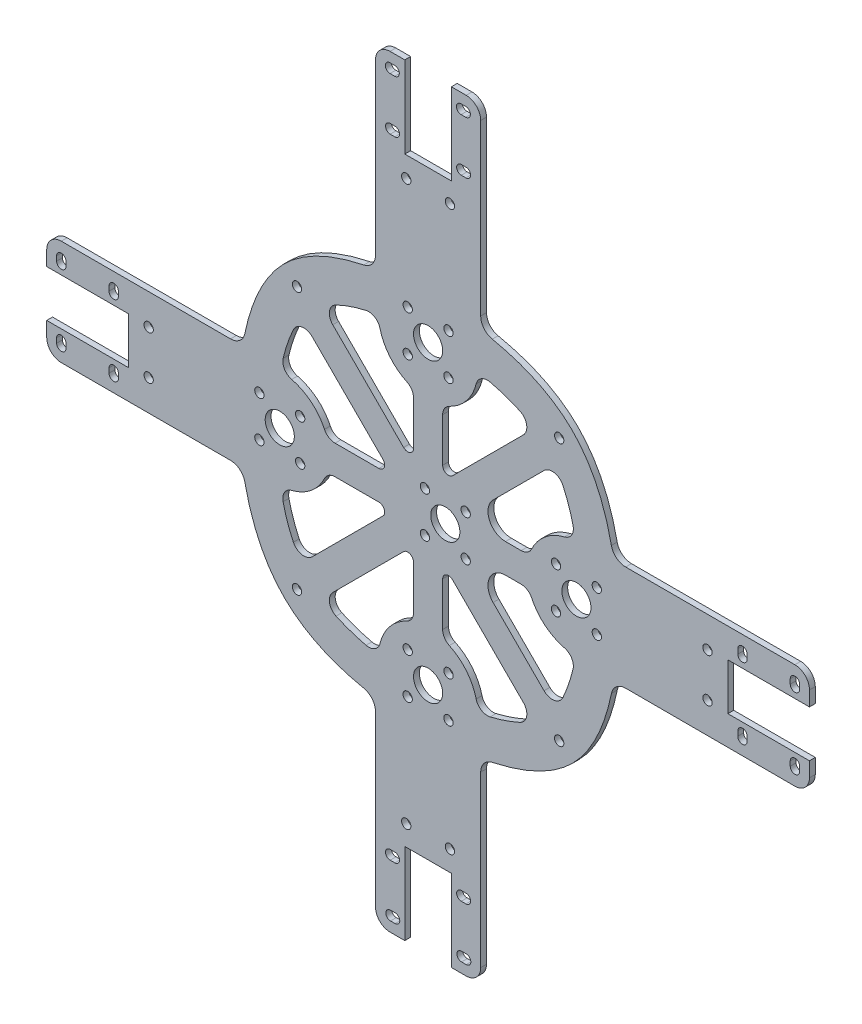
SolidWorks part; units mm, degrees
ref_plane "Front Plane" through (0, 0, 0) normal (0, 0, 1) x (1, 0, 0)
ref_plane "Top Plane" through (0, 0, 0) normal (0, 1, 0) x (1, 0, 0)
ref_plane "Right Plane" through (0, 0, 0) normal (1, 0, 0) x (0, 0, -1)
sketch "Sketch1" plane through (0, 0, 157.1733) normal (0, 0, 1) x (1, 0, 0)
  line L0 (24.8571, 138.0093) -> (24.8571, 36.186) construction
  line L1 (75.7688, 87.0977) -> (-26.0546, 87.0977) construction
  line L2 (24.8571, 87.0977) -> (74.3546, 136.5951) construction
  line L3 (24.8571, 87.0977) -> (-24.6404, 136.5951) construction
  line L4 (24.8571, 87.0977) -> (74.3546, 37.6002) construction
  line L5 (24.8571, 87.0977) -> (-24.6404, 37.6002) construction
  line L6 (24.8571, 36.186) -> (24.8571, -73.1097) construction
  line L7 (-4.7101, -8.814) -> (52.2591, -8.814) construction
  line L8 (6.7991, -38.814) -> (6.7991, 19.2863)
  line L9 (32.8571, -43.814) -> (37.9151, -43.814)
  line L10 (42.9151, -38.814) -> (42.9151, 19.2918)
  line L11 (11.7991, -43.814) -> (16.8571, -43.814)
  line L12 (16.8571, -43.814) -> (16.8571, -15.814)
  line L13 (16.8571, -15.814) -> (32.8571, -15.814)
  line L14 (32.8571, -15.814) -> (32.8571, -43.814)
  line L15 (11.8571, -19.214) -> (13.4571, -19.214)
  line L16 (13.4571, -22.414) -> (11.8571, -22.414)
  line L17 (37.8571, -19.214) -> (36.2571, -19.214)
  line L18 (37.8571, -22.414) -> (36.2571, -22.414)
  line L19 (37.9382, -40.414) -> (36.3382, -40.414)
  line L20 (13.5382, -40.414) -> (11.9382, -40.414)
  line L21 (-101.0546, 105.1556) -> (-42.9534, 105.1556)
  line L22 (11.9382, -37.214) -> (13.5382, -37.214)
  line L23 (37.9382, -37.214) -> (36.3382, -37.214)
  line L24 (-106.0546, 79.0977) -> (-106.0546, 74.0397)
  line L25 (-101.0546, 69.0397) -> (-42.9487, 69.0397)
  line L26 (-106.0546, 100.1556) -> (-106.0546, 95.0977)
  line L27 (-106.0546, 95.0977) -> (-78.0546, 95.0977)
  line L28 (-78.0546, 95.0977) -> (-78.0546, 79.0977)
  line L29 (-78.0546, 79.0977) -> (-106.0546, 79.0977)
  line L30 (-81.4546, 100.0977) -> (-81.4546, 98.4977)
  line L31 (-84.6546, 98.4977) -> (-84.6546, 100.0977)
  line L32 (-81.4546, 74.0977) -> (-81.4546, 75.6977)
  line L33 (-84.6546, 74.0977) -> (-84.6546, 75.6977)
  line L34 (-102.6546, 74.0165) -> (-102.6546, 75.6165)
  line L35 (-102.6546, 98.4165) -> (-102.6546, 100.0165)
  line L36 (-99.4546, 100.0165) -> (-99.4546, 98.4165)
  line L37 (-99.4546, 74.0165) -> (-99.4546, 75.6165)
  line L38 (-26.0546, 87.0977) -> (-135.3502, 87.0977) construction
  line L39 (-71.0546, 116.6649) -> (-71.0546, 59.6957) construction
  line L40 (42.9151, 213.0093) -> (42.9151, 154.909)
  line L41 (16.8571, 218.0093) -> (11.7991, 218.0093)
  line L42 (6.7991, 213.0093) -> (6.7991, 154.9075)
  line L43 (37.9151, 218.0093) -> (32.8571, 218.0093)
  line L44 (32.8571, 218.0093) -> (32.8571, 190.0093)
  line L45 (32.8571, 190.0093) -> (16.8571, 190.0093)
  line L46 (16.8571, 190.0093) -> (16.8571, 218.0093)
  line L47 (37.8571, 193.4093) -> (36.2571, 193.4093)
  line L48 (36.2571, 196.6093) -> (37.8571, 196.6093)
  line L49 (11.8571, 193.4093) -> (13.4571, 193.4093)
  line L50 (11.8571, 196.6093) -> (13.4571, 196.6093)
  line L51 (11.776, 214.6093) -> (13.376, 214.6093)
  line L52 (36.176, 214.6093) -> (37.776, 214.6093)
  line L53 (37.776, 211.4093) -> (36.176, 211.4093)
  line L54 (11.776, 211.4093) -> (13.376, 211.4093)
  line L55 (24.8571, 138.0093) -> (24.8571, 247.305) construction
  line L56 (54.4243, 183.0093) -> (-2.5449, 183.0093) construction
  line L57 (150.7688, 69.0397) -> (92.7039, 69.1257)
  line L58 (155.7688, 95.0977) -> (155.7688, 100.1556)
  line L59 (150.7688, 105.1556) -> (92.6636, 105.1556)
  line L60 (155.7688, 74.0397) -> (155.7688, 79.0977)
  line L61 (155.7688, 79.0977) -> (127.7688, 79.0977)
  line L62 (127.7688, 79.0977) -> (127.7688, 95.0977)
  line L63 (127.7688, 95.0977) -> (155.7688, 95.0977)
  line L64 (131.1688, 74.0977) -> (131.1688, 75.6977)
  line L65 (134.3688, 75.6977) -> (134.3688, 74.0977)
  line L66 (131.1688, 100.0977) -> (131.1688, 98.4977)
  line L67 (134.3688, 100.0977) -> (134.3688, 98.4977)
  line L68 (152.3688, 100.1788) -> (152.3688, 98.5788)
  line L69 (152.3688, 75.7788) -> (152.3688, 74.1788)
  line L70 (149.1688, 74.1788) -> (149.1688, 75.7788)
  line L71 (149.1688, 100.1788) -> (149.1688, 98.5788)
  line L72 (75.7688, 87.0977) -> (185.0644, 87.0977) construction
  line L73 (120.7688, 57.5304) -> (120.7688, 114.4996) construction
  line L76 (-42.9487, 69.0397) -> (-42.9427, 69.0397)
  line L81 (42.9151, 154.909) -> (42.9151, 154.9053)
  circle A0 centre (17.3571, -8.814) radius 1.6
  circle A1 centre (32.3571, -8.814) radius 1.6
  arc A2 (42.9151, 19.2918) -> (46.8658, 24.1805) centre (47.9151, 19.2918) cw
  arc A3 (6.7991, 19.2863) -> (2.7951, 24.1861) centre (1.7991, 19.2863) ccw
  arc A4 (42.9151, -38.814) -> (37.9151, -43.814) centre (37.9151, -38.814) cw
  arc A5 (6.7991, -38.814) -> (11.7991, -43.814) centre (11.7991, -38.814) ccw
  arc A6 (11.8571, -19.214) -> (11.8571, -22.414) centre (11.8571, -20.814) ccw
  arc A7 (11.9382, -37.214) -> (11.9382, -40.414) centre (11.9382, -38.814) ccw
  arc A8 (37.8571, -19.214) -> (37.8571, -22.414) centre (37.8571, -20.814) cw
  arc A9 (36.3382, -40.414) -> (36.3382, -37.214) centre (36.3382, -38.814) cw
  arc A10 (13.5382, -40.414) -> (13.5382, -37.214) centre (13.5382, -38.814) ccw
  arc A11 (13.4571, -22.414) -> (13.4571, -19.214) centre (13.4571, -20.814) ccw
  arc A12 (37.9382, -37.214) -> (37.9382, -40.414) centre (37.9382, -38.814) cw
  arc A13 (36.2571, -22.414) -> (36.2571, -19.214) centre (36.2571, -20.814) cw
  circle A14 centre (-71.0546, 94.5977) radius 1.6
  circle A15 centre (-71.0546, 79.5977) radius 1.6
  arc A16 (-38.0477, 65.0591) -> (-42.9427, 69.0397) centre (-42.9427, 64.0397) ccw
  arc A17 (46.8977, 150.0099) -> (42.9151, 154.9053) centre (47.9151, 154.9053) cw
  arc A18 (-101.0546, 69.0397) -> (-106.0546, 74.0397) centre (-101.0546, 74.0397) cw
  arc A19 (-101.0546, 105.1556) -> (-106.0546, 100.1556) centre (-101.0546, 100.1556) ccw
  arc A20 (-81.4546, 100.0977) -> (-84.6546, 100.0977) centre (-83.0546, 100.0977) ccw
  arc A21 (-99.4546, 100.0165) -> (-102.6546, 100.0165) centre (-101.0546, 100.0165) ccw
  arc A22 (-81.4546, 74.0977) -> (-84.6546, 74.0977) centre (-83.0546, 74.0977) cw
  arc A23 (-102.6546, 75.6165) -> (-99.4546, 75.6165) centre (-101.0546, 75.6165) cw
  arc A24 (-102.6546, 98.4165) -> (-99.4546, 98.4165) centre (-101.0546, 98.4165) ccw
  arc A25 (-84.6546, 98.4977) -> (-81.4546, 98.4977) centre (-83.0546, 98.4977) ccw
  arc A26 (-99.4546, 74.0165) -> (-102.6546, 74.0165) centre (-101.0546, 74.0165) cw
  arc A27 (-84.6546, 75.6977) -> (-81.4546, 75.6977) centre (-83.0546, 75.6977) cw
  circle A28 centre (32.3571, 183.0093) radius 1.6
  circle A29 centre (17.3571, 183.0093) radius 1.6
  arc A30 (87.7994, 65.1351) -> (92.7039, 69.1257) centre (92.6965, 64.1258) cw
  arc A31 (87.7682, 109.1387) -> (92.6636, 105.1556) centre (92.6636, 110.1556) ccw
  arc A32 (6.7991, 213.0093) -> (11.7991, 218.0093) centre (11.7991, 213.0093) cw
  arc A33 (42.9151, 213.0093) -> (37.9151, 218.0093) centre (37.9151, 213.0093) ccw
  arc A34 (37.8571, 193.4093) -> (37.8571, 196.6093) centre (37.8571, 195.0093) ccw
  arc A35 (37.776, 211.4093) -> (37.776, 214.6093) centre (37.776, 213.0093) ccw
  arc A36 (11.8571, 193.4093) -> (11.8571, 196.6093) centre (11.8571, 195.0093) cw
  arc A37 (13.376, 214.6093) -> (13.376, 211.4093) centre (13.376, 213.0093) cw
  arc A38 (36.176, 214.6093) -> (36.176, 211.4093) centre (36.176, 213.0093) ccw
  arc A39 (36.2571, 196.6093) -> (36.2571, 193.4093) centre (36.2571, 195.0093) ccw
  arc A40 (11.776, 211.4093) -> (11.776, 214.6093) centre (11.776, 213.0093) cw
  arc A41 (13.4571, 196.6093) -> (13.4571, 193.4093) centre (13.4571, 195.0093) cw
  circle A42 centre (120.7688, 79.5977) radius 1.6
  circle A43 centre (120.7688, 94.5977) radius 1.6
  arc A44 (2.8163, 150.012) -> (6.7991, 154.9075) centre (1.7991, 154.9075) ccw
  arc A45 (-38.058, 109.1381) -> (-42.9534, 105.1556) centre (-42.9534, 110.1556) cw
  arc A46 (150.7688, 105.1556) -> (155.7688, 100.1556) centre (150.7688, 100.1556) cw
  arc A47 (150.7688, 69.0397) -> (155.7688, 74.0397) centre (150.7688, 74.0397) ccw
  arc A48 (131.1688, 74.0977) -> (134.3688, 74.0977) centre (132.7688, 74.0977) ccw
  arc A49 (149.1688, 74.1788) -> (152.3688, 74.1788) centre (150.7688, 74.1788) ccw
  arc A50 (131.1688, 100.0977) -> (134.3688, 100.0977) centre (132.7688, 100.0977) cw
  arc A51 (152.3688, 98.5788) -> (149.1688, 98.5788) centre (150.7688, 98.5788) cw
  arc A52 (152.3688, 75.7788) -> (149.1688, 75.7788) centre (150.7688, 75.7788) ccw
  arc A53 (134.3688, 75.6977) -> (131.1688, 75.6977) centre (132.7688, 75.6977) ccw
  arc A54 (149.1688, 100.1788) -> (152.3688, 100.1788) centre (150.7688, 100.1788) cw
  arc A55 (134.3688, 98.4977) -> (131.1688, 98.4977) centre (132.7688, 98.4977) cw
  spline S0 degree 3 poles (46.8658, 24.1805) (57.6421, 26.4935) (77.1441, 34.8421) (85.5664, 54.301) (87.7994, 65.1351) knots 0.049347 0.049347 0.049347 0.049347 0.125 0.200866 0.200866 0.200866 0.200866
  spline S1 degree 3 poles (-38.0477, 65.0591) (-35.8019, 54.2758) (-27.373, 34.8677) (-8.0057, 26.3816) (2.7951, 24.1861) knots 0.799368 0.799368 0.799368 0.799368 0.875 0.950653 0.950653 0.950653 0.950653
  spline S2 degree 3 poles (2.8163, 150.012) (-7.9739, 147.77) (-27.3849, 139.3427) (-35.8155, 119.9275) (-38.058, 109.1381) knots 0.549351 0.549351 0.549351 0.549351 0.625 0.700642 0.700642 0.700642 0.700642
  spline S3 degree 3 poles (87.7682, 109.1387) (85.5262, 119.931) (77.1034, 139.3394) (57.6888, 147.7672) (46.8977, 150.0099) knots 0.29934 0.29934 0.29934 0.29934 0.375 0.450651 0.450651 0.450651 0.450651
  point P5 (24.8571, 152.0977)
  point P14 (89.8571, 87.0977)
  point P16 (24.8571, 22.0977)
  point P18 (-40.1429, 87.0977)
  point P20 (24.8571, 87.0977)
  point P42 (42.9151, -43.814)
  point P45 (6.7991, -43.814)
  point P96 (-106.0546, 69.0397)
  point P99 (-106.0546, 105.1556)
  point P146 (6.7991, 218.0093)
  point P149 (42.9151, 218.0093)
  point P196 (155.7688, 105.1556)
  point P199 (155.7688, 69.0397)
  point P228 (24.8571, 87.0977)
  dimension "D1" = 5
  dimension "D2" = 5
  dimension "D3" = 5
  dimension "D4" = 5
  dimension "D6" = 5
  dimension "D7" = 5
  dimension "D5" = 0
extrude "Boss-Extrude1" add sketch "Sketch1" along normal blind 2
sketch "Sketch5" plane through (0, 0, 159.1733) normal (0, 0, 1) x (1, 0, 0)
  circle A0 centre (30.7688, 87.0977) radius 5
  circle A1 centre (75.7688, 87.0977) radius 5
  circle A2 centre (-26.0546, 87.0977) radius 5
  circle A3 centre (24.8571, 36.186) radius 5
  circle A4 centre (24.8571, 138.0093) radius 5
extrude "Cut-Extrude1" cut sketch "Sketch5" against normal blind 2
sketch "Sketch7" plane through (0, 0, 159.1733) normal (0, 0, 1) x (1, 0, 0)
  circle A0 centre (-20.1429, 132.0977) radius 1.6
  circle A1 centre (69.8571, 132.0977) radius 1.6
  circle A2 centre (-20.1429, 42.0977) radius 1.6
  circle A3 centre (69.8571, 42.0977) radius 1.6
  dimension "D1" = 45
  dimension "D2" = 45
  dimension "D3" = 45
  dimension "D4" = 45
  dimension "D5" = 45
  dimension "D6" = 45
  dimension "D7" = 45
  dimension "D8" = 45
extrude "Cut-Extrude2" cut sketch "Sketch7" against normal blind 2
sketch "Sketch9" plane through (0, 0, 159.1733) normal (0, 0, 1) x (1, 0, 0)
  line L6 (-7.869, 126.8948) -> (16.4429, 102.5829)
  line L7 (-14.9401, 119.8237) -> (9.3718, 95.5119)
  line L8 (19.8571, 55.1596) -> (19.8571, 70.1982)
  line L9 (29.8571, 119.0357) -> (29.8571, 103.9971)
  line L10 (-14.9401, 54.3716) -> (9.3718, 78.6834)
  line L11 (-7.869, 47.3005) -> (16.4429, 71.6124)
  line L12 (56.7951, 92.0977) -> (51.4134, 92.0977)
  line L13 (-7.0809, 82.0977) -> (7.9576, 82.0977)
  line L15 (7.9576, 92.0977) -> (-7.0809, 92.0977)
  line L16 (19.8571, 103.9971) -> (19.8571, 119.0357)
  line L18 (33.2713, 102.5829) -> (57.5832, 126.8948)
  line L21 (47.1708, 102.3403) -> (64.6542, 119.8237)
  line L22 (47.1708, 71.855) -> (64.6542, 54.3716)
  line L23 (29.8571, 70.1982) -> (29.8571, 55.1596)
  line L27 (33.2713, 71.6124) -> (57.5832, 47.3005)
  line L28 (51.4134, 82.0977) -> (56.7951, 82.0977)
  arc A0 (-21.9709, 70.5954) -> (-10.695, 79.8119) centre (-26.0546, 87.0977) ccw
  arc A1 (8.3549, 133.9256) -> (17.5714, 122.6497) centre (24.8571, 138.0093) ccw
  arc A2 (71.6851, 103.5999) -> (60.4091, 94.3834) centre (75.7688, 87.0977) ccw
  arc A3 (41.3593, 40.2697) -> (32.1428, 51.5456) centre (24.8571, 36.186) ccw
  arc A4 (-10.695, 94.3834) -> (-21.9709, 103.5999) centre (-26.0546, 87.0977) ccw
  arc A5 (32.1428, 122.6497) -> (41.3593, 133.9256) centre (24.8571, 138.0093) ccw
  arc A6 (60.4091, 79.8119) -> (71.6851, 70.5954) centre (75.7688, 87.0977) ccw
  arc A7 (17.5714, 51.5456) -> (8.3549, 40.2697) centre (24.8571, 36.186) ccw
  arc A8 (33.2713, 71.6124) -> (29.8571, 70.1982) centre (31.8571, 70.1982) ccw
  arc A9 (19.8571, 70.1982) -> (16.4429, 71.6124) centre (17.8571, 70.1982) ccw
  arc A10 (47.1708, 71.855) -> (51.4134, 82.0977) centre (51.4134, 76.0977) cw
  arc A11 (51.4134, 92.0977) -> (47.1708, 102.3403) centre (51.4134, 98.0977) cw
  arc A12 (33.2713, 102.5829) -> (29.8571, 103.9971) centre (31.8571, 103.9971) cw
  arc A13 (9.3718, 78.6834) -> (7.9576, 82.0977) centre (7.9576, 80.0977) ccw
  arc A14 (19.8571, 103.9971) -> (16.4429, 102.5829) centre (17.8571, 103.9971) cw
  arc A15 (9.3718, 95.5119) -> (7.9576, 92.0977) centre (7.9576, 94.0977) cw
  arc A16 (71.6851, 103.5999) -> (74.6162, 108.4062) centre (70.7242, 107.4828) ccw
  arc A17 (71.6851, 70.5954) -> (74.6162, 65.7891) centre (70.7242, 66.7125) cw
  arc A18 (64.6542, 54.3716) -> (71.0978, 55.4881) centre (67.4827, 57.2) ccw
  arc A19 (64.6542, 119.8237) -> (71.0978, 118.7073) centre (67.4827, 116.9953) cw
  arc A20 (41.3593, 40.2697) -> (46.1657, 37.3386) centre (45.2422, 41.2305) ccw
  arc A21 (-7.869, 47.3005) -> (-6.7525, 40.8569) centre (-5.0406, 44.4721) ccw
  arc A22 (8.3549, 40.2697) -> (3.5485, 37.3386) centre (4.472, 41.2305) cw
  arc A23 (57.5832, 47.3005) -> (56.4667, 40.8569) centre (54.7548, 44.4721) cw
  arc A24 (-21.9709, 70.5954) -> (-24.902, 65.7891) centre (-21.01, 66.7125) ccw
  arc A25 (-14.9401, 54.3716) -> (-21.3836, 55.4881) centre (-17.7685, 57.2) cw
  arc A26 (-21.9709, 103.5999) -> (-24.902, 108.4062) centre (-21.01, 107.4828) cw
  arc A27 (-14.9401, 119.8237) -> (-21.3836, 118.7073) centre (-17.7685, 116.9953) ccw
  arc A28 (-7.0809, 82.0977) -> (-10.695, 79.8119) centre (-7.0809, 78.0977) ccw
  arc A29 (-10.695, 94.3834) -> (-7.0809, 92.0977) centre (-7.0809, 96.0977) ccw
  arc A30 (29.8571, 55.1596) -> (32.1428, 51.5456) centre (33.8571, 55.1596) ccw
  arc A31 (19.8571, 55.1596) -> (17.5714, 51.5456) centre (15.8571, 55.1596) cw
  arc A32 (56.7951, 82.0977) -> (60.4091, 79.8119) centre (56.7951, 78.0977) cw
  arc A33 (56.7951, 92.0977) -> (60.4091, 94.3834) centre (56.7951, 96.0977) ccw
  arc A34 (29.8571, 119.0357) -> (32.1428, 122.6497) centre (33.8571, 119.0357) cw
  arc A35 (17.5714, 122.6497) -> (19.8571, 119.0357) centre (15.8571, 119.0357) cw
  arc A36 (8.3549, 133.9256) -> (3.5485, 136.8567) centre (4.472, 132.9648) ccw
  arc A37 (-7.869, 126.8948) -> (-6.7525, 133.3384) centre (-5.0406, 129.7232) cw
  arc A38 (57.5832, 126.8948) -> (56.4667, 133.3384) centre (54.7548, 129.7232) ccw
  arc A39 (41.3593, 133.9256) -> (46.1657, 136.8567) centre (45.2422, 132.9648) cw
  arc A40 (-24.902, 108.4062) -> (-21.3836, 118.7073) centre (30.2562, 95.3182) cw
  arc A41 (-6.7525, 133.3384) -> (3.5485, 136.8567) centre (13.8814, 89.765) cw
  arc A42 (46.1657, 136.8567) -> (56.4667, 133.3384) centre (33.0776, 81.6985) cw
  arc A43 (71.0978, 118.7073) -> (74.6162, 108.4062) centre (27.5244, 98.0733) cw
  arc A44 (74.6162, 65.7891) -> (71.0978, 55.4881) centre (19.458, 78.8771) cw
  arc A45 (46.1657, 37.3386) -> (56.4667, 40.8569) centre (33.0776, 92.4968) ccw
  arc A46 (3.5485, 37.3386) -> (-6.7525, 40.8569) centre (16.6365, 92.4968) cw
  arc A47 (-21.3836, 55.4881) -> (-24.902, 65.7891) centre (22.1897, 76.122) cw
  point P1 (24.8571, 22.0977)
  point P2 (89.8571, 87.0977)
  dimension "D1" = 4
  dimension "D2" = 6
extrude "Cut-Extrude9" cut sketch "Sketch9" against normal blind 2
sketch "Sketch10" plane through (0, 0, 159.1733) normal (0, 0, 1) x (1, 0, 0)
  circle A0 centre (17.8571, 145.0093) radius 1.6
  circle A1 centre (31.8571, 145.0093) radius 1.6
  circle A2 centre (17.8571, 131.0093) radius 1.6
  circle A3 centre (31.8571, 131.0093) radius 1.6
  circle A4 centre (68.7688, 80.0977) radius 1.6
  circle A5 centre (82.7688, 94.0977) radius 1.6
  circle A6 centre (82.7688, 80.0977) radius 1.6
  circle A7 centre (68.7688, 94.0977) radius 1.6
  circle A8 centre (-33.0546, 94.0977) radius 1.6
  circle A9 centre (-19.0546, 80.0977) radius 1.6
  circle A10 centre (-33.0546, 80.0977) radius 1.6
  circle A11 centre (-19.0546, 94.0977) radius 1.6
  circle A12 centre (31.8571, 29.186) radius 1.6
  circle A13 centre (31.8571, 43.186) radius 1.6
  circle A14 centre (17.8571, 43.186) radius 1.6
  circle A15 centre (17.8571, 29.186) radius 1.6
  circle A16 centre (37.7688, 80.0977) radius 1.6
  circle A17 centre (23.7688, 80.0977) radius 1.6
  circle A18 centre (23.7688, 94.0977) radius 1.6
  circle A19 centre (37.7688, 94.0977) radius 1.6
extrude "Cut-Extrude10" cut sketch "Sketch10" against normal blind 2
ref_axis "Axis1" through (32.3571, -8.814, 171.3027) along (0, 0, -1)
ref_axis "Axis2" through (17.3571, -8.814, 172.2996) along (0, 0, -1)
ref_axis "Axis3" through (11.8571, -20.814, 179.078) along (0, 0, -1)
ref_axis "Axis4" through (11.9382, -38.814, 177.1293) along (0, 0, -1)
